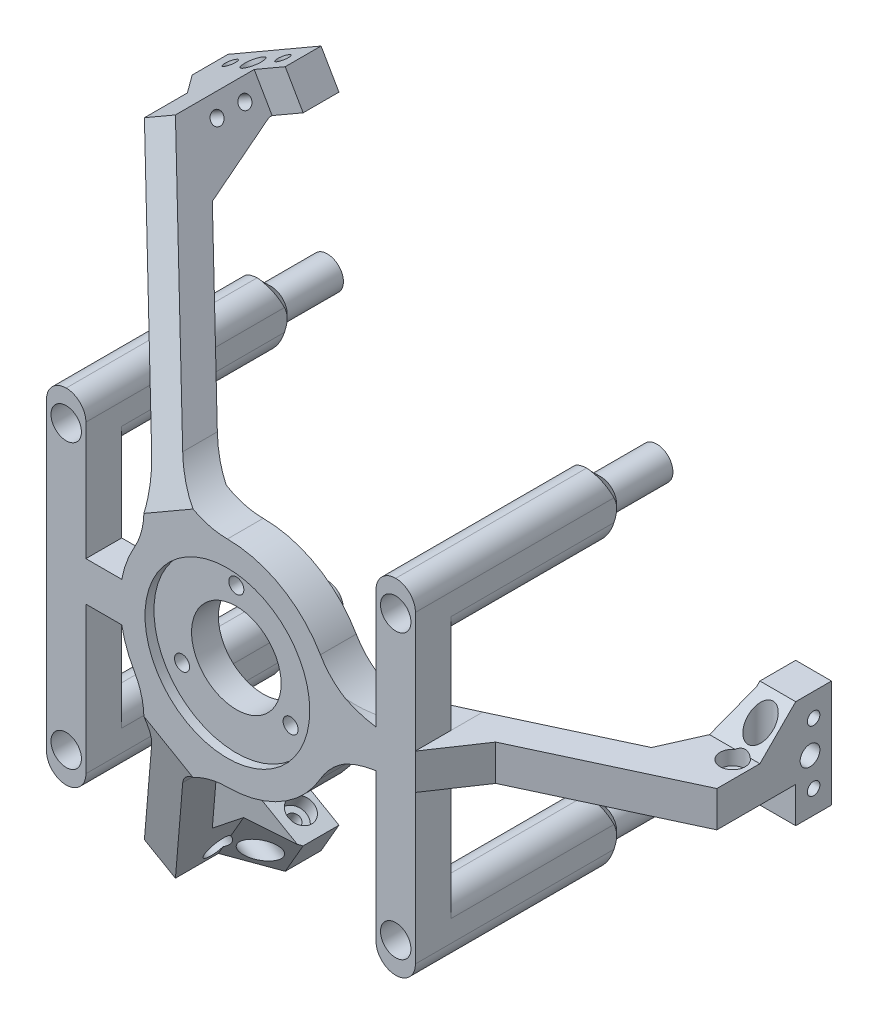
SolidWorks part; units mm, degrees
ref_plane "Plan de face" through (0, 0, 0) normal (0, 0, 1) x (1, 0, 0)
ref_plane "Plan de dessus" through (0, 0, 0) normal (0, 1, 0) x (1, 0, 0)
ref_plane "Plan de droite" through (0, 0, 0) normal (1, 0, 0) x (0, 0, -1)
sketch "Esquisse1" plane through (0, 0, 0) normal (0, 0, 1) x (1, 0, 0)
  line L0 (0, 0) -> (93.67, 0) construction
  line L1 (93.67, 15) -> (103.67, 15)
  line L2 (93.67, 15) -> (93.67, -15)
  line L3 (93.67, -15) -> (103.67, -15)
  line L4 (103.67, 15) -> (103.67, -15)
  line L5 (-33.8446, -88.6206) -> (-59.8254, -73.6206)
  line L6 (-33.8446, -88.6206) -> (-38.8446, -97.2809)
  line L7 (-38.8446, -97.2809) -> (-64.8254, -82.2809)
  line L8 (-59.8254, -73.6206) -> (-64.8254, -82.2809)
  line L9 (-59.8254, 73.6206) -> (-33.8446, 88.6206)
  line L10 (-59.8254, 73.6206) -> (-64.8254, 82.2809)
  line L11 (-64.8254, 82.2809) -> (-38.8446, 97.2809)
  line L12 (-33.8446, 88.6206) -> (-38.8446, 97.2809)
  point P17 (0, 0)
  dimension "D1" = 30
  dimension "D2" = 10
  dimension "D3" = 93.67
  dimension "D4" = 3
extrude "Boss.-Extru.1" add sketch "Esquisse1" along normal blind 10
sketch "Esquisse2" plane through (0, 0, 10) normal (0, 0, 1) x (1, 0, 0)
  line L0 (-57.0272, 86.7831) -> (-46.3532, 92.9458)
  line L1 (-38.8446, 97.2809) -> (-64.8254, 82.2809) construction
  line L2 (93.67, 15) -> (93.67, -15) construction
  line L3 (93.67, 5) -> (103.67, 5)
  line L4 (93.67, 5) -> (93.67, -5)
  line L5 (93.67, -5) -> (103.67, -5)
  line L6 (103.67, 5) -> (103.67, -5)
  line L7 (103.67, -15) -> (103.67, 15) construction
  line L8 (-42.5049, -83.6206) -> (-51.1651, -78.6206)
  line L9 (-42.5049, -83.6206) -> (-47.5049, -92.2809)
  line L10 (-47.5049, -92.2809) -> (-56.1651, -87.2809)
  line L11 (-51.1651, -78.6206) -> (-56.1651, -87.2809)
  line L12 (-51.1651, 78.6206) -> (-42.5049, 83.6206)
  line L13 (-51.1651, 78.6206) -> (-56.1651, 87.2809)
  line L14 (-56.1651, 87.2809) -> (-47.5049, 92.2809)
  line L15 (-42.5049, 83.6206) -> (-47.5049, 92.2809)
  point P12 (93.67, 0)
  point P13 (93.67, 0)
  point P24 (0, 0)
  line M6 (-59.8254, 73.6206) -> (-33.8446, 88.6206)
  dimension "D1" = 3
extrude "Boss.-Extru.2" add sketch "Esquisse2" along normal blind 45 contours L15 L0 L13 M6 | L6 L3 L4 L5 | L8 L11 L10 L9 region at (-49.335, 85.4507, 10) region at (98.67, 0, 10) region at (-49.335, -85.4507, 10)
sketch "Esquisse3" plane through (0, 0, 55) normal (0, 0, 1) x (1, 0, 0)
  line L0 (103.67, 5) -> (103.67, -5) construction
  line L1 (-47.5049, -92.2809) -> (-56.1651, -87.2809) construction
  line L2 (-47.5049, 92.2809) -> (-56.1651, 87.2809) construction
  line L3 (103.67, 5) -> (103.67, -5)
  line L4 (-47.5049, -92.2809) -> (-56.1651, -87.2809)
  line L5 (-47.5049, 92.2809) -> (-56.1651, 87.2809)
  line L6 (-56.1651, -87.2809) -> (-19.1203, -23.1174)
  line L7 (-47.5049, -92.2809) -> (-10.4601, -28.1174)
  line L8 (103.67, -5) -> (29.5804, -5)
  line L9 (103.67, 5) -> (29.5804, 5)
  line L10 (-56.1651, 87.2809) -> (-19.1203, 23.1174)
  line L11 (-47.5049, 92.2809) -> (-10.4601, 28.1174)
  line L12 (-51.1651, -78.6206) -> (-56.1651, -87.2809) construction
  line L13 (-42.5049, -83.6206) -> (-47.5049, -92.2809) construction
  line L14 (93.67, -5) -> (103.67, -5) construction
  line L15 (93.67, 5) -> (103.67, 5) construction
  line L16 (-51.1651, 78.6206) -> (-56.1651, 87.2809) construction
  line L17 (-42.5049, 83.6206) -> (-47.5049, 92.2809) construction
  arc A0 (-19.1203, -23.1174) -> (-19.1203, 23.1174) centre (0, 0) cw
  arc A1 (-10.4601, 28.1174) -> (29.5804, 5) centre (0, 0) cw
  arc A2 (29.5804, -5) -> (-10.4601, -28.1174) centre (0, 0) cw
  dimension "D1" = 30
extrude "Boss.-Extru.3" add sketch "Esquisse3" along normal blind 10
chamfer "Chanfrein1" distance 28 angle 65 3 edges at (93.67, 0, 55) (-46.835, -81.1206, 55) (-46.835, 81.1206, 55) first distance on face at (93.67, 0, 18.75) first distance on face at (-46.835, -81.1206, 18.75) first distance on face at (-46.835, 81.1206, 18.75)
chamfer "Chanfrein2" distance 33 angle 65 3 edges at (-51.835, -89.7809, 65) (-51.835, 89.7809, 65) (103.67, 0, 65) first distance on face at (-51.835, -89.7809, 21.25) first distance on face at (-51.835, 89.7809, 21.25) first distance on face at (103.67, 0, 21.25)
fillet "Congé1" radius 20 6 edges at (29.5804, -5, 60) (-10.4601, -28.1174, 60) (-19.1203, -23.1174, 60) (-19.1203, 23.1174, 60) (29.5804, 5, 60) (-10.4601, 28.1174, 60)
chamfer "Chanfrein4" distance 10 angle 41 3 edges at (-46.835, -81.1206, 27) (93.67, 0, 27) (-46.835, 81.1206, 27) first distance on face at (-28.4061, -49.2008, 44.1871) first distance on face at (56.8122, 0, 44.1871) first distance on face at (-28.4061, 49.2008, 44.1871)
sketch "Esquisse4" plane through (0, 0, 65) normal (0, 0, 1) x (1, 0, 0)
  circle A0 centre (0, 0) radius 12.5
  dimension "D1" = 25
extrude "Enlèv. mat.-Extru.1" cut sketch "Esquisse4" against normal up to next
sketch "Esquisse5" plane through (0, 0, 65) normal (0, 0, 1) x (1, 0, 0)
  circle A0 centre (0, 0) radius 23
  dimension "D1" = 46
extrude "Enlèv. mat.-Extru.2" cut sketch "Esquisse5" against normal blind 2.5
sketch "Esquisse6" plane through (0, 0, 62.5) normal (0, 0, 1) x (1, 0, 0)
  line L0 (0, 17.5) -> (0, 0) construction
  circle A0 centre (0, 17.5) radius 2.1
  circle A1 centre (15.1554, -8.75) radius 2.1
  circle A2 centre (-15.1554, -8.75) radius 2.1
  point P10 (0, 0)
  dimension "D2" = 4.2
  dimension "D1" = 17.5
  dimension "D3" = 3
extrude "Enlèv. mat.-Extru.3" cut sketch "Esquisse6" against normal up to next
sketch "Esquisse7" plane through (0, 0, 55) normal (0, 0, -1) x (-1, 0, 0)
  line L0 (0, 0) -> (39.5, 0) construction
  line L1 (-41.5, -52) -> (-52.5, -52)
  line L2 (-41.5, -52) -> (-41.5, 44)
  line L3 (-41.5, 44) -> (-52.5, 44)
  line L4 (-52.5, -52) -> (-52.5, 44)
  line L5 (50.5, -52) -> (39.5, -52)
  line L6 (39.5, -52) -> (39.5, -5.5)
  line L7 (39.5, -5.5) -> (29.4915, -5.5)
  line L8 (50.5, -52) -> (50.5, 44)
  line L9 (50.5, 44) -> (39.5, 44)
  line L10 (39.5, 44) -> (39.5, 5.5)
  line L11 (39.5, 5.5) -> (29.4915, 5.5)
  line L12 (39.5, -5.5) -> (39.5, 5.5) construction
  arc A0 (25.9808, -15) -> (25.9808, 15) centre (0, 0) ccw construction
  arc A1 (29.4915, -5.5) -> (29.4915, 5.5) centre (0, 0) ccw
  point P7 (-47, 44)
  point P21 (45, 44)
  point P22 (39.5, 0)
  dimension "D1" = 11
  dimension "D2" = 52
  dimension "D3" = 96
  dimension "D4" = 47
  dimension "D5" = 92
extrude "Boss.-Extru.4" add sketch "Esquisse7" along normal blind 43.3 and the other way up to surface (10 mm away) other way up to face at (23, 0, 65)
sketch "Esquisse8" plane through (0, 0, 11.7) normal (0, 0, -1) x (-1, 0, 0)
  line L0 (-52.5, -4) -> (50.5, -4) construction
  line L1 (-52.5, 44) -> (-52.5, -52) construction
  line L2 (50.5, -52) -> (50.5, 44) construction
  line L3 (45, 35.5) -> (-47, 35.5) construction
  line L4 (-1, -4) -> (-1, 35.5) construction
  line L5 (-52.5, -52) -> (-41.5, -52) construction
  circle A0 centre (45, 35.5) radius 4.25
  circle A1 centre (-47, 35.5) radius 4.25
  circle A2 centre (-47, -43.5) radius 4.25
  circle A3 centre (45, -43.5) radius 4.25
  dimension "D4" = 8.5
  dimension "D1" = 92
  dimension "D2" = 79
  dimension "D3" = 8.5
extrude "Enlèv. mat.-Extru.4" cut sketch "Esquisse8" against normal up to next
sketch "Esquisse18" plane through (0, 0, 11.7) normal (0, 0, -1) x (-1, 0, 0)
  circle A0 centre (-47, 35.5) radius 4.5
  circle A1 centre (-47, -43.5) radius 4.5
  circle A2 centre (45, 35.5) radius 4.5
  circle A3 centre (45, -43.5) radius 4.5
  circle A12 centre (45, 35.5) radius 2.5
  circle A13 centre (-47, 35.5) radius 2.5
  circle A14 centre (-47, -43.5) radius 2.5
  circle A15 centre (45, -43.5) radius 2.5
  dimension "D1" = 9
  dimension "D2" = 5
extrude "Boss.-Extru.6" add sketch "Esquisse18" along normal blind 17.6
chamfer "Chanfrein3" distance 3.9 angle 45 4 edges at (42.5, -43.5, 11.7) (42.5, 35.5, 11.7) (-49.5, -43.5, 11.7) (-49.5, 35.5, 11.7)
sketch "Esquisse19" plane through (0, 0, -5.9) normal (0, 0, -1) x (-1, 0, 0)
  circle A0 centre (-47, -43.5) radius 4.5 construction
  circle A1 centre (-47, 35.5) radius 4.5 construction
  circle A2 centre (45, 35.5) radius 4.5 construction
  circle A3 centre (45, -43.5) radius 4.5 construction
  circle A4 centre (-47, -43.5) radius 4.5
  circle A5 centre (-47, 35.5) radius 4.5
  circle A6 centre (45, 35.5) radius 4.5
  circle A7 centre (45, -43.5) radius 4.5
  circle A8 centre (-47, -43.5) radius 1.5
  circle A9 centre (-47, 35.5) radius 1.5
  circle A10 centre (45, 35.5) radius 1.5
  circle A11 centre (45, -43.5) radius 1.5
  dimension "D1" = 3
extrude "Boss.-Extru.7" add sketch "Esquisse19" along normal blind 2
sketch "Esquisse10" plane through (0, 0, 11.7) normal (0, 0, -1) x (-1, 0, 0)
  line L6 (50.5, -52) -> (50.5, -49.849) construction
  line L7 (50.5, -35) -> (29.4915, -35)
  line L8 (50.5, -35) -> (50.5, 27)
  line L9 (50.5, 27) -> (29.4915, 27)
  line L10 (29.4915, -35) -> (29.4915, 27)
  line L11 (45, 35.5) -> (45, 27) construction
  line L12 (45, -43.5) -> (45, -35) construction
  line L13 (-52.5, 44) -> (-52.5, 41.849) construction
  line L14 (-52.5, 27) -> (-41.5, 27)
  line L15 (-52.5, 27) -> (-52.5, -35)
  line L16 (-52.5, -35) -> (-41.5, -35)
  line L17 (-41.5, 27) -> (-41.5, -35)
  line L18 (-41.5, -52) -> (-41.5, -49.849) construction
  dimension "D1" = 8.5
extrude "Enlèv. mat.-Extru.6" cut sketch "Esquisse10" against normal up to surface (43.3 mm away) up to face at (-2.1, 17.5, 55)
sketch "Esquisse17" plane through (0, 0, 55) normal (0, 0, -1) x (-1, 0, 0)
  line L0 (-41.5, -5.0813) -> (-52.5, -5)
  line L1 (-52.5, -5) -> (-52.5, 5)
  line L2 (-52.5, 5) -> (-41.5, 5.0813)
  line L3 (-41.5, 5.0813) -> (-41.5, -5.0813)
extrude "Boss.-Extru.5" add sketch "Esquisse17" along normal up to surface (8.8021 mm away) contours L3 L0 L1 L2 up to face at (68.5535, 0, 38.712)
fillet "Congé2" radius 5.5 16 edges at (-50.5, 44, 38.35) (-39.5, 44, 38.35) (41.5, 44, 38.35) (52.5, 44, 38.35) (-50.5, -52, 38.35) (-39.5, -52, 38.35) (52.5, -52, 38.35) (41.5, -52, 38.35) (-50.5, 27, 33.35) (-39.5, 27, 33.35) (-50.5, -35, 33.35) (-39.5, -35, 33.35) (41.5, -35, 33.35) (52.5, -35, 33.35) (41.5, 27, 33.35) (52.5, 27, 33.35)
sketch "Esquisse20" plane through (30.7728, 0, 65.9925) normal (0.4226, 0, 0.9063) x (0.9063, 0, -0.4226)
  line L2 (11.8361, -5.0813) -> (11.8361, 5.0813)
  line L3 (2.3485, 7.9167) -> (2.3485, -7.9167)
  line L4 (11.8361, -5.0813) -> (11.8361, 5.0813)
  line L5 (2.3485, 7.9167) -> (2.3485, -7.9167)
  ellipse E2 centre (13.8236, 25) end of major axis (35.8912, 25) minor radius 20 (2.3485, 7.9167) -> (11.8361, 5.0813) ccw
  ellipse E3 centre (13.8236, -25) end of major axis (35.8912, -25) minor radius 20 (11.8361, -5.0813) -> (2.3485, -7.9167) ccw
  ellipse E4 centre (13.8236, 25) end of major axis (35.8912, 25) minor radius 20 (2.3485, 7.9167) -> (11.8361, 5.0813) ccw
  ellipse E5 centre (13.8236, -25) end of major axis (35.8912, -25) minor radius 20 (11.8361, -5.0813) -> (2.3485, -7.9167) ccw
  dimension "D1" = 0
extrude "Boss.-Extru.8" add sketch "Esquisse20" along normal up to surface (4.4242 mm away) up to face at (42.75, -43.5, 65)
chamfer "Chanfrein6" distance 10 angle 31 1 edges at (52.5, 0, 55.861) first distance on face at (78.085, 0, 43.9305)
sketch "Esquisse11" plane through (4.3301, -2.5, 0) normal (0.866, -0.5, 0) x (0, 0, -1)
  line L0 (-10.8702, -93.67) -> (-10, -93.67) construction
  line L1 (-10, -93.67) -> (-10, -103.67) construction
  circle A0 centre (-15, -98.86) radius 1.75
  circle A1 centre (-22.78, -98.86) radius 1.75
  dimension "D4" = 3.5
  dimension "D1" = 5.19
  dimension "D2" = 5
  dimension "D3" = 7.78
extrude "Enlèv. mat.-Extru.7" cut sketch "Esquisse11" against normal up to next
sketch "Esquisse12" plane through (4.3301, -2.5, 0) normal (0.866, -0.5, 0) x (0, 0, -1)
  circle A0 centre (-15, -98.86) radius 3.5
  circle A1 centre (-22.78, -98.86) radius 3.5
  dimension "D1" = 7
extrude "Enlèv. mat.-Extru.8" cut sketch "Esquisse12" against normal blind 4
sketch "Esquisse13" plane through (-46.835, -81.1206, 0) normal (0.5, 0.866, 0) x (0.866, -0.5, 0)
  line L0 (-15, -10) -> (-15, 0) construction
  line L1 (-15, -5) -> (-8.5, -5) construction
  line L2 (15, -5) -> (8.5, -5) construction
  line L3 (15, -10) -> (15, 0) construction
  circle A0 centre (-8.5, -5) radius 1.75
  circle A1 centre (8.5, -5) radius 1.75
  dimension "D2" = 3.5
  dimension "D1" = 6.5
extrude "Enlèv. mat.-Extru.9" cut sketch "Esquisse13" against normal up to next
sketch "Esquisse14" plane through (-46.835, -81.1206, 0) normal (0.5, 0.866, 0) x (0.866, -0.5, 0)
  circle A0 centre (-8.5, -5) radius 3.5
  circle A1 centre (8.5, -5) radius 3.5
  dimension "D1" = 7
extrude "Enlèv. mat.-Extru.10" cut sketch "Esquisse14" against normal blind 4
sketch "Esquisse15" plane through (-46.835, -81.1206, 0) normal (0.5, 0.866, 0) x (0.866, -0.5, 0)
  line L0 (15, 0) -> (-15, 0) construction
  line L1 (-15, -10) -> (-15, 0) construction
  circle A0 centre (0, -6) radius 2.75
  point P5 (0, 0)
  point P8 (-15, -5)
  dimension "D1" = 5.5
  dimension "D2" = 1
extrude "Enlèv. mat.-Extru.11" cut sketch "Esquisse15" against normal up to next
pattern_circular "Répétition circulaire1" count 3 over 360 about axis through (0, 0, -0.001) along (0, 0, 1) of "Enlèv. mat.-Extru.7", "Enlèv. mat.-Extru.11", "Enlèv. mat.-Extru.10", "Enlèv. mat.-Extru.9", "Enlèv. mat.-Extru.8" reverse direction yes
chamfer "Chanfrein5" distance 10 angle 45 3 edges at (98.67, 5, 10) (-45.0049, -87.9507, 10) (-53.6651, 82.9507, 10)
